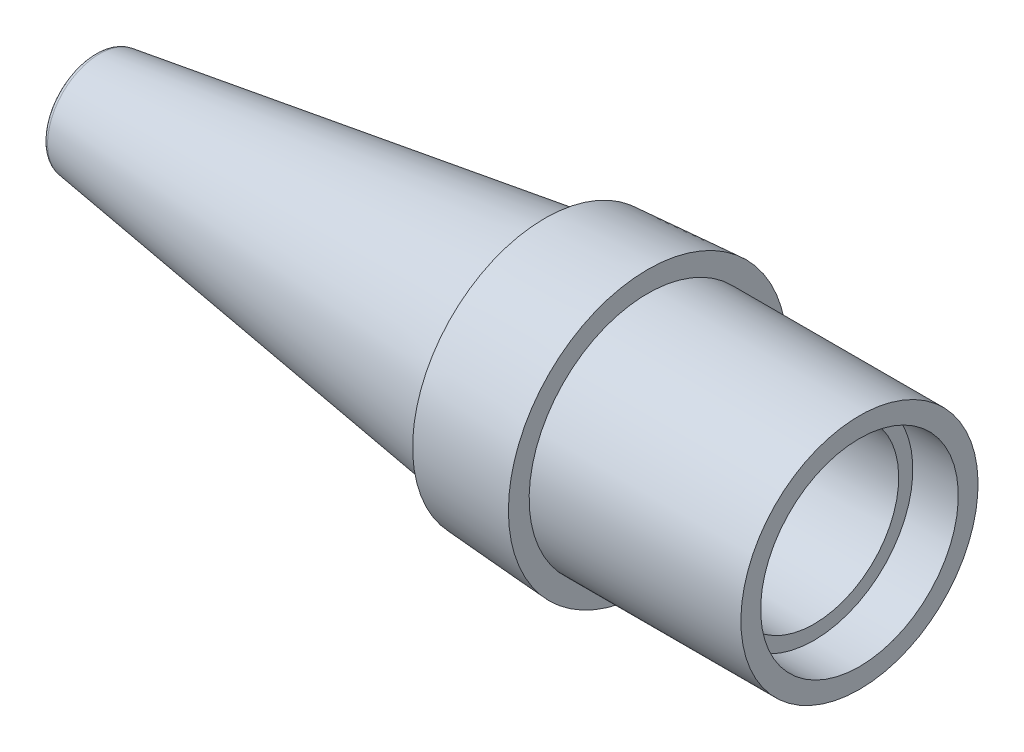
SolidWorks part; units mm, degrees
ref_plane "Plano frontal" through (0, 0, 0) normal (0, 0, 1) x (1, 0, 0)
ref_plane "Plano superior" through (0, 0, 0) normal (0, 1, 0) x (1, 0, 0)
ref_plane "Plano direito" through (0, 0, 0) normal (1, 0, 0) x (0, 0, -1)
sketch "Esboço1" plane through (0, 0, 0) normal (0, 0, 1) x (1, 0, 0)
  line L0 (0, 0) -> (25.48, 0) construction
  line L1 (15.95, 4.6873) -> (19.59, 4.935)
  line L2 (0.1714, 1.8398) -> (15.7786, 4.0952)
  line L3 (15.95, 4.2932) -> (15.95, 4.6873)
  line L4 (9.5543, 2.7307) -> (0, 1.35)
  line L5 (19.59, 4.935) -> (19.59, 3.4)
  line L6 (20.59, 3.65) -> (25.48, 3.65)
  line L7 (25.48, 3.65) -> (25.48, 3)
  line L8 (25.48, 3) -> (9.5543, 2.7307)
  line L9 (0, 1.6418) -> (0, 1.35)
  line L11 (19.59, 3.4) -> (20.59, 3.4)
  line L12 (20.59, 3.4) -> (20.59, 3.65)
  arc A0 (0.1714, 1.8398) -> (0, 1.6418) centre (0.2, 1.6418) ccw
  arc A1 (15.7786, 4.0952) -> (15.95, 4.2932) centre (15.75, 4.2932) ccw
  point P5 (0, 4.21)
  point P6 (25.48, 4.21)
  point P16 (0, 1.815)
  point P19 (15.95, 4.12)
  dimension "D12" = 0.2
  dimension "D13" = 0.2
  dimension "D1" = 25.48
  dimension "D2" = 9.3746
  dimension "D3" = 7.3
  dimension "D4" = 5.89
  dimension "D5" = 3.64
  dimension "D6" = 9.87
  dimension "D7" = 8.24
  dimension "D8" = 3.63
  dimension "D9" = 6
  dimension "D10" = 15.9257
  dimension "D11" = 2.7
  dimension "D14" = 6.8
  dimension "D15" = 1
revolve "Revolução1" add sketch "Esboço1" angle 360 about L0
sketch "Esboço3" plane through (0, 0, 0) normal (0, 1, 0) x (1, 0, 0)
  line L0 (25.7687, -3.98) -> (25.48, -3.48)
  line L1 (25.48, -3.48) -> (25.1913, -3.98)
  line L2 (25.1913, -3.98) -> (25.7687, -3.98)
  line L3 (25.48, -3.48) -> (25.48, -3.98) construction
  line L4 (25.48, -3.65) -> (25.48, 3.65) construction
  line L5 (0, 0) -> (25.48, 0) construction
  line L6 (25.48, -3) -> (25.48, 3) construction
  dimension "D1" = 60
  dimension "D2" = 6.96
  dimension "D3" = 0.5
sketch "Esboço4" plane through (25.48, 0, 0) normal (1, 0, 0) x (0, 0, -1)
  circle A0 centre (0, 0) radius 3.48
curve "Hélice/Espiral1" pitch 0.29 height 5.8 turns 20
sweep "Varredura de corte1" cut profiles "Esboço3" path "Hélice/Espiral1"
sketch "Esboço5" plane through (0, 0, 0) normal (0, 0, 1) x (1, 0, 0)
  line L1 (19.59, 4.935) -> (19.59, 3.4) construction
  line L2 (19.59, 3.5) -> (27.09, 3.5)
  line L3 (19.59, 4.2) -> (19.59, 3.5)
  line L4 (19.59, 4.2) -> (27.09, 4.2)
  line L5 (27.09, 4.2) -> (27.09, 3.5)
  line L6 (18.1773, 0) -> (25.7141, 0) construction
  line L7 (0, 0) -> (25.48, 0) construction
  dimension "D1" = 8.4
  dimension "D2" = 7.5
  dimension "D3" = 7
revolve "Revolução2" add sketch "Esboço5" angle 360 about L6
